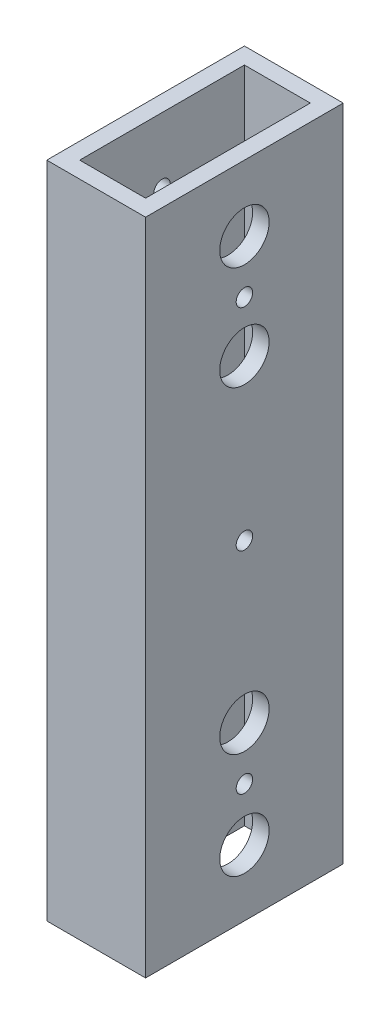
SolidWorks part; units mm, degrees
ref_plane "Front" through (0, 0, 0) normal (0, 0, 1) x (1, 0, 0)
ref_plane "Top" through (0, 0, 0) normal (0, 1, 0) x (1, 0, 0)
ref_plane "Right" through (0, 0, 0) normal (1, 0, 0) x (0, 0, -1)
sketch "Sketch1" plane through (0, 0, 0) normal (0, 1, 0) x (1, 0, 0)
  line L0 (3.175, 3.175) -> (15.875, 3.175)
  line L1 (0, 0) -> (19.05, 0)
  line L2 (0, 0) -> (0, 38.1)
  line L3 (0, 38.1) -> (19.05, 38.1)
  line L4 (19.05, 0) -> (19.05, 38.1)
  line L5 (15.875, 3.175) -> (15.875, 34.925)
  line L6 (3.175, 34.925) -> (15.875, 34.925)
  line L7 (3.175, 3.175) -> (3.175, 34.925)
  dimension "D1" = 38.1
  dimension "D2" = 19.05
  dimension "D3" = 3.175
extrude "Boss-Extrude1" add sketch "Sketch1" along normal blind 127
sketch "Sketch2" plane through (19.05, 0, 0) normal (1, 0, 0) x (0, 0, -1)
  line L0 (19.05, 0) -> (19.05, 12.7) construction
  line L1 (0, 0) -> (38.1, 0) construction
  line L2 (19.05, 12.7) -> (19.05, 32.7) construction
  line L3 (0, 63.5) -> (38.1, 63.5) construction
  line L4 (0, 127) -> (0, 0) construction
  line L5 (38.1, 127) -> (38.1, 0) construction
  line L6 (19.05, 114.3) -> (19.05, 94.3) construction
  circle A0 centre (19.05, 12.7) radius 1.5875
  circle A1 centre (19.05, 32.7) radius 1.5875
  circle A2 centre (19.05, 94.3) radius 1.5875
  circle A3 centre (19.05, 114.3) radius 1.5875
  dimension "D2" = 3.175
  dimension "D1" = 12.7
  dimension "D3" = 20
extrude "Cut-Extrude1" cut sketch "Sketch2" against normal through all
sketch "Sketch3" plane through (19.05, 0, 0) normal (1, 0, 0) x (0, 0, -1)
  circle A0 centre (19.05, 114.3) radius 4.7625
  circle A1 centre (19.05, 94.3) radius 4.7625
  circle A2 centre (19.05, 33.0594) radius 4.7625
  circle A4 centre (19.05, 12.7) radius 4.7625
  dimension "D1" = 9.525
extrude "Cut-Extrude2" cut sketch "Sketch3" against normal up to next
sketch "Sketch4" plane through (19.05, 0, 0) normal (1, 0, 0) x (0, 0, -1)
  line L0 (19.05, 28.2969) -> (19.05, 17.4625) construction
  line L1 (0, 63.5) -> (38.1, 63.5) construction
  line L2 (0, 127) -> (0, 0) construction
  line L3 (38.1, 127) -> (38.1, 0) construction
  circle A0 centre (19.05, 33.0594) radius 4.7625 construction
  circle A1 centre (19.05, 12.7) radius 4.7625 construction
  circle A2 centre (19.05, 22.8797) radius 1.5875
  circle A3 centre (19.05, 63.5) radius 1.5875
  circle A4 centre (19.05, 104.1203) radius 1.5875
  dimension "D1" = 3.175
extrude "Cut-Extrude3" cut sketch "Sketch4" against normal through all
sketch "Sketch5" plane through (0, 0, 0) normal (-1, 0, 0) x (0, 0, 1)
  circle A0 centre (-19.05, 104.1203) radius 4.7625
  circle A1 centre (-19.05, 63.5) radius 4.7625
  circle A2 centre (-19.05, 22.8797) radius 4.7625
  dimension "D1" = 9.525
extrude "Cut-Extrude4" cut sketch "Sketch5" against normal up to next
